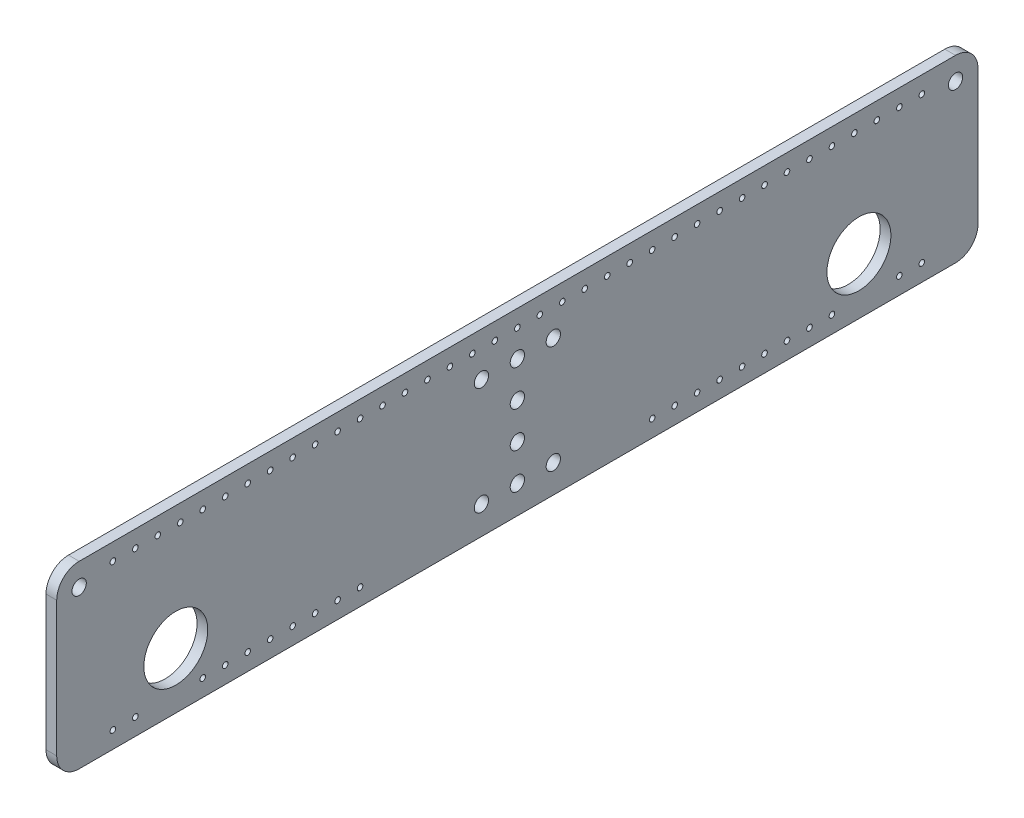
SolidWorks part; units mm, degrees
ref_plane "Front Plane" through (0, 0, 0) normal (0, 0, 1) x (1, 0, 0)
ref_plane "Top Plane" through (0, 0, 0) normal (0, 1, 0) x (1, 0, 0)
ref_plane "Right Plane" through (0, 0, 0) normal (1, 0, 0) x (0, 0, -1)
sketch "Sketch2" plane through (0, 0, 0) normal (1, 0, 0) x (0, 0, -1)
  line L0 (-23.4723, 28.6683) -> (-23.4723, -31.3317)
  line L1 (-13.4723, 38.6683) -> (376.5277, 38.6683)
  line L2 (-13.4723, -41.3317) -> (376.5277, -41.3317)
  line L3 (386.5277, 28.6683) -> (386.5277, -31.3317)
  circle A1 centre (29.5277, -16.3317) radius 14.225
  circle A2 centre (333.5277, -16.3317) radius 14.225
  arc A15 (-23.4723, 28.6683) -> (-13.4723, 38.6683) centre (-13.4723, 28.6683) cw
  arc A16 (-13.4723, -41.3317) -> (-23.4723, -31.3317) centre (-13.4723, -31.3317) cw
  arc A17 (386.5277, 28.6683) -> (376.5277, 38.6683) centre (376.5277, 28.6683) ccw
  arc A18 (376.5277, -41.3317) -> (386.5277, -31.3317) centre (376.5277, -31.3317) ccw
  circle A59 centre (181.5277, -28.7717) radius 3.18
  circle A60 centre (197.5277, -28.7717) radius 3.18
  circle A63 centre (197.5277, 19.2283) radius 3.18
  circle A64 centre (181.5277, -12.7717) radius 3.18
  circle A65 centre (181.5277, 3.2283) radius 3.18
  circle A66 centre (181.5277, 19.2283) radius 3.18
  circle A67 centre (165.5277, -28.7717) radius 3.18
  circle A68 centre (165.5277, 19.2283) radius 3.18
  circle A69 centre (197.5277, -12.7717) radius 3.18 [skipped]
  circle A70 centre (197.5277, 3.2283) radius 3.18 [skipped]
  circle A71 centre (-8.4723, 31.1683) radius 1.25 construction
  circle A152 centre (1.5277, 31.1683) radius 1.25
  circle A153 centre (11.5277, 31.1683) radius 1.25
  circle A154 centre (21.5277, 31.1683) radius 1.25
  circle A155 centre (31.5277, 31.1683) radius 1.25
  circle A156 centre (41.5277, 31.1683) radius 1.25
  circle A157 centre (51.5277, 31.1683) radius 1.25
  circle A158 centre (61.5277, 31.1683) radius 1.25
  circle A159 centre (71.5277, 31.1683) radius 1.25
  circle A160 centre (81.5277, 31.1683) radius 1.25
  circle A161 centre (91.5277, 31.1683) radius 1.25
  circle A162 centre (101.5277, 31.1683) radius 1.25
  circle A163 centre (111.5277, 31.1683) radius 1.25
  circle A164 centre (121.5277, 31.1683) radius 1.25
  circle A165 centre (131.5277, 31.1683) radius 1.25
  circle A166 centre (141.5277, 31.1683) radius 1.25
  circle A167 centre (151.5277, 31.1683) radius 1.25
  circle A168 centre (161.5277, 31.1683) radius 1.25
  circle A169 centre (171.5277, 31.1683) radius 1.25
  circle A170 centre (181.5277, 31.1683) radius 1.25
  circle A171 centre (191.5277, 31.1683) radius 1.25
  circle A172 centre (201.5277, 31.1683) radius 1.25
  circle A173 centre (211.5277, 31.1683) radius 1.25
  circle A174 centre (221.5277, 31.1683) radius 1.25
  circle A175 centre (231.5277, 31.1683) radius 1.25
  circle A176 centre (241.5277, 31.1683) radius 1.25
  circle A177 centre (251.5277, 31.1683) radius 1.25
  circle A178 centre (261.5277, 31.1683) radius 1.25
  circle A179 centre (271.5277, 31.1683) radius 1.25
  circle A180 centre (281.5277, 31.1683) radius 1.25
  circle A181 centre (291.5277, 31.1683) radius 1.25
  circle A182 centre (301.5277, 31.1683) radius 1.25
  circle A183 centre (311.5277, 31.1683) radius 1.25
  circle A184 centre (321.5277, 31.1683) radius 1.25
  circle A185 centre (331.5277, 31.1683) radius 1.25
  circle A186 centre (341.5277, 31.1683) radius 1.25
  circle A187 centre (351.5277, 31.1683) radius 1.25
  circle A188 centre (361.5277, 31.1683) radius 1.25
  circle A190 centre (1.5277, -33.8317) radius 1.25
  circle A191 centre (11.5277, -33.8317) radius 1.25
  circle A194 centre (41.5277, -33.8317) radius 1.25
  circle A195 centre (51.5277, -33.8317) radius 1.25
  circle A196 centre (61.5277, -33.8317) radius 1.25
  circle A197 centre (71.5277, -33.8317) radius 1.25
  circle A198 centre (81.5277, -33.8317) radius 1.25
  circle A199 centre (91.5277, -33.8317) radius 1.25
  circle A200 centre (101.5277, -33.8317) radius 1.25
  circle A201 centre (111.5277, -33.8317) radius 1.25
  circle A214 centre (241.5277, -33.8317) radius 1.25
  circle A215 centre (251.5277, -33.8317) radius 1.25
  circle A216 centre (261.5277, -33.8317) radius 1.25
  circle A217 centre (271.5277, -33.8317) radius 1.25
  circle A218 centre (281.5277, -33.8317) radius 1.25
  circle A219 centre (291.5277, -33.8317) radius 1.25
  circle A220 centre (301.5277, -33.8317) radius 1.25
  circle A221 centre (311.5277, -33.8317) radius 1.25
  circle A222 centre (321.5277, -33.8317) radius 1.25
  circle A225 centre (351.5277, -33.8317) radius 1.25
  circle A226 centre (361.5277, -33.8317) radius 1.25
  circle A229 centre (181.5277, -33.8317) radius 1.25 [skipped]
  circle A230 centre (201.5277, -33.8317) radius 1.25 [skipped]
  circle A231 centre (161.5277, -33.8317) radius 1.25 [skipped]
  circle A232 centre (151.5277, -33.8317) radius 1.25 [skipped]
  circle A233 centre (141.5277, -33.8317) radius 1.25 [skipped]
  circle A234 centre (131.5277, -33.8317) radius 1.25 [skipped]
  circle A235 centre (171.5277, -33.8317) radius 1.25 [skipped]
  circle A236 centre (191.5277, -33.8317) radius 1.25 [skipped]
  circle A237 centre (211.5277, -33.8317) radius 1.25 [skipped]
  circle A238 centre (221.5277, -33.8317) radius 1.25 [skipped]
  circle A239 centre (231.5277, -33.8317) radius 1.25 [skipped]
  circle A240 centre (31.5277, -33.8317) radius 1.25 [skipped]
  circle A241 centre (21.5277, -33.8317) radius 1.25 [skipped]
  circle A242 centre (331.5277, -33.8317) radius 1.25 [skipped]
  circle A243 centre (341.5277, -33.8317) radius 1.25 [skipped]
  circle A245 centre (-13.4723, 28.6683) radius 3.18
  circle A247 centre (376.5277, 28.6683) radius 3.18
  circle A248 centre (371.5277, 31.1683) radius 1.25 [skipped]
  circle A249 centre (371.5277, -33.8317) radius 1.25 [skipped]
  circle A250 centre (-8.4723, -33.8317) radius 1.25 [skipped]
  circle A257 centre (121.5277, -33.8317) radius 1.25 [skipped]
  point P32 (-23.4723, 38.6683)
  point P35 (-23.4723, -41.3317)
  point P40 (386.5277, -41.3317)
  point P123 (181.5277, -41.3317)
  dimension "D3" = 25
  dimension "D7" = 10
  dimension "D8" = 10
  dimension "D9" = 10
  dimension "D10" = 10
  dimension "D11" = 7.5
  dimension "D13" = 12.56
  dimension "D1" = 80
  dimension "D2" = 410
  dimension "D4" = 53
  dimension "D5" = 25
  dimension "D6" = 53
  dimension "D12" = 15
  dimension "D14" = 205
  dimension "D15" = 2
  dimension "D16" = 4
  dimension "D17" = 2
  dimension "D18" = 39
  dimension "D19" = 2
extrude "Boss-Extrude1" add sketch "Sketch2" along normal blind 4.7625
